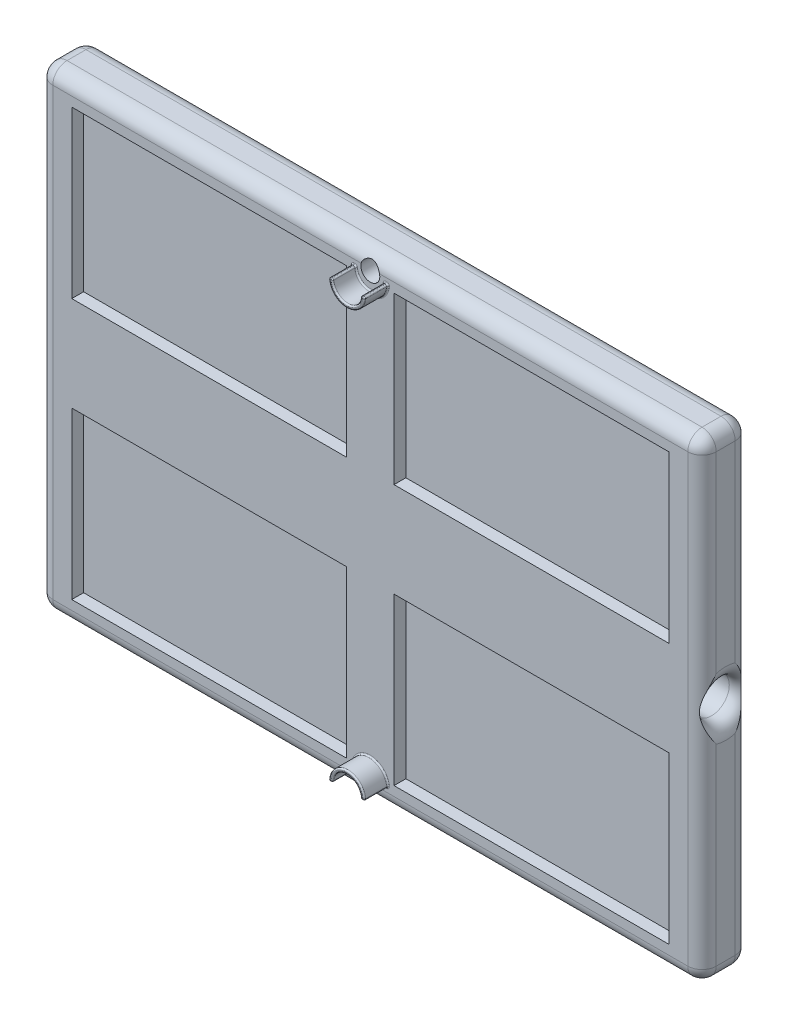
SolidWorks part; units mm, degrees
ref_plane "Front Plane" through (0, 0, 0) normal (0, 0, 1) x (1, 0, 0)
ref_plane "Top Plane" through (0, 0, 0) normal (0, 1, 0) x (1, 0, 0)
ref_plane "Right Plane" through (0, 0, 0) normal (1, 0, 0) x (0, 0, -1)
sketch "Sketch1" plane through (0, 0, 0) normal (0, 0, 1) x (1, 0, 0)
  line L1 (-70, 50) -> (70, 50)
  line L2 (-70, 50) -> (-70, -50)
  line L3 (-70, -50) -> (70, -50)
  line L4 (70, 50) -> (70, -50)
  line L5 (-70, 50) -> (70, -50) construction
  line L6 (-70, -50) -> (70, 50) construction
  point P0 (0, 0)
  dimension "D1" = 140
  dimension "D2" = 100
extrude "Boss-Extrude1" add sketch "Sketch1" along normal blind 10
sketch "Sketch2" plane through (0, 0, 10) normal (0, 0, 1) x (1, 0, 0)
  line L0 (0, 56.6746) -> (0, -57.672) construction
  line L1 (-63, 45) -> (-5, 45)
  line L2 (-63, 45) -> (-63, 10)
  line L3 (-63, 10) -> (-5, 10)
  line L4 (-5, 45) -> (-5, 10)
  line L5 (-63, 45) -> (-5, 10) construction
  line L6 (-63, 10) -> (-5, 45) construction
  line L7 (5, 45) -> (5, 10)
  line L8 (63, 10) -> (5, 10)
  line L9 (63, 45) -> (63, 10)
  line L10 (63, 45) -> (5, 45)
  line L11 (-81.139, 0) -> (84.2718, 0) construction
  line L12 (63, -45) -> (63, -10)
  line L13 (63, -45) -> (5, -45)
  line L14 (5, -45) -> (5, -10)
  line L15 (63, -10) -> (5, -10)
  line L16 (-5, -45) -> (-5, -10)
  line L17 (-63, -45) -> (-63, -10)
  line L18 (-63, -10) -> (-5, -10)
  line L19 (-63, -45) -> (-5, -45)
  point P0 (-34, 27.5)
  dimension "D1" = 58
  dimension "D2" = 35
  dimension "D3" = 10
  dimension "D4" = 5
extrude "Cut-Extrude1" cut sketch "Sketch2" against normal blind 2.5
sketch "Sketch4" plane through (70, 0, 0) normal (1, 0, 0) x (0, 0, -1)
  line L0 (0, -50) -> (0, 50) construction
  line L2 (-10, -50) -> (0, -50) construction
  circle A0 centre (-5, 0) radius 3.75
  point P6 (-4.3084, -50)
  dimension "D1" = 7.5
  dimension "D2" = 5
  dimension "D3" = 50
extrude "Cut-Extrude2" cut sketch "Sketch4" against normal blind 140
sketch "Sketch5" plane through (0, 0, 10) normal (0, 0, 1) x (1, 0, 0)
  line L0 (70, 50) -> (-70, 50) construction
  line L1 (3.75, 46) -> (-3.75, 46)
  line L2 (-83.7319, 0) -> (106.9104, 0) construction
  line L3 (-5, 10) -> (-5, 45) construction
  line L4 (3.75, -46) -> (-3.75, -46)
  circle A0 centre (0, 46) radius 3.75
  circle A1 centre (0, 46) radius 3
  circle A2 centre (0, -46) radius 3
  circle A3 centre (0, -46) radius 3.75
  dimension "D1" = 7.5
  dimension "D4" = 6
  dimension "D2" = 4
  dimension "D3" = 5
extrude "Boss-Extrude3" add sketch "Sketch5" along normal blind 5 contours A1 L1 A0 | A3 L4 A2 region at (0, 42.3339, 10) region at (3.375, -45.9161, 10)
sketch "Sketch6" plane through (0, 0, 10) normal (0, 0, 1) x (1, 0, 0)
  line L0 (-70, -50) -> (70, -50) construction
  line L4 (5, -10) -> (5, -45) construction
  line L5 (-78.5375, 0) -> (120.2834, 0) construction
  circle A0 centre (0, -46.5) radius 2
  circle A3 centre (0, 46.5) radius 2
  dimension "D1" = 4
  dimension "D2" = 3.5
  dimension "D3" = 5
extrude "Cut-Extrude3" cut sketch "Sketch6" against normal blind 10
fillet "Fillet1" radius 3 14 edges at (0, 50, 10) (0, 50, 0) (-70, 50, 5) (-70, 0, 10) (-70, 0, 0) (-70, 3.75, 5) (70, 0, 10) (70, 50, 5) (70, 0, 0) (70, 3.75, 5) (-70, -50, 5) (0, -50, 10) (70, -50, 5) (0, -50, 0)
fillet "Fillet7" radius 0.3 24 edges at (0, 42.25, 10) (0, 43, 10) (-3, 46, 12.5) (-3.75, 46, 12.5) (-3.375, 46, 10) (3.75, 46, 12.5) (3, 46, 12.5) (3.375, 46, 10) (3.375, 46, 15) (0, 42.25, 15) (-3.375, 46, 15) (0, 43, 15) (-3.375, -46, 10) (3.375, -46, 10) (-3, -46, 12.5) (3, -46, 12.5) (0, -43, 10) (3.375, -46, 15) (0, -43, 15) (-3.375, -46, 15) (3.75, -46, 12.5) (0, -42.25, 15) (-3.75, -46, 12.5) (0, -42.25, 10)
